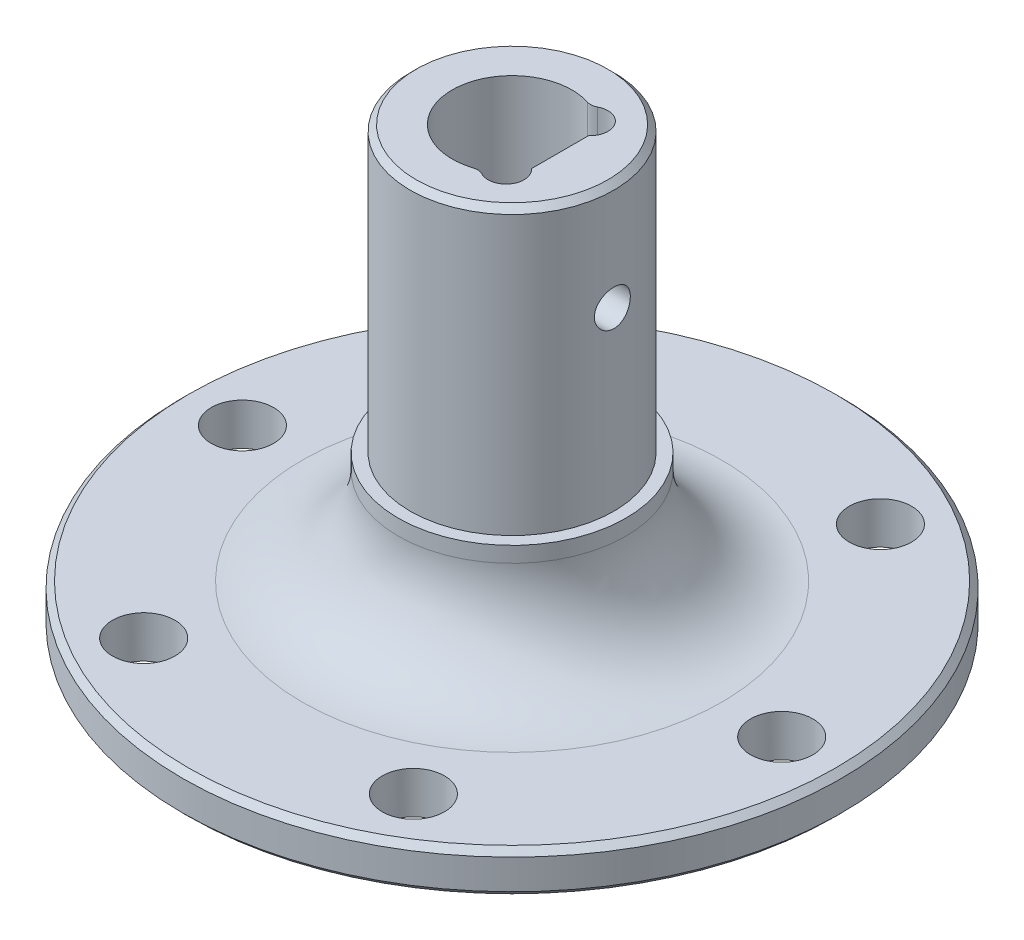
SolidWorks part; units mm, degrees
material "6061-T6 (SS)"
ref_plane "前视基准面" through (0, 0, 0) normal (0, 0, 1) x (1, 0, 0)
ref_plane "上视基准面" through (0, 0, 0) normal (0, 1, 0) x (1, 0, 0)
ref_plane "右视基准面" through (0, 0, 0) normal (1, 0, 0) x (0, 0, -1)
sketch "草图1" plane through (0, 0, 0) normal (0, 1, 0) x (1, 0, 0)
  circle A0 centre (0, 0) radius 10
  dimension "D1" = 20
extrude "凸台-拉伸1" add sketch "草图1" along normal blind 1
sketch "草图2" plane through (0, 1, 0) normal (0, 1, 0) x (1, 0, 0)
  circle A0 centre (0, 0) radius 27.5
  dimension "D1" = 55
extrude "凸台-拉伸2" add sketch "草图2" along normal blind 3.5
sketch "草图3" plane through (0, 4.5, 0) normal (0, 1, 0) x (1, 0, 0)
  circle A0 centre (0, 0) radius 8.5
  dimension "D1" = 17
extrude "凸台-拉伸3" add sketch "草图3" along normal blind 33
sketch "草图4" plane through (0, 37.5, 0) normal (0, 1, 0) x (1, 0, 0)
  circle A0 centre (0, 0) radius 5
  dimension "D1" = 10
extrude "切除-拉伸1" cut sketch "草图4" against normal blind 20
sketch "草图7" plane through (0, 1, 0) normal (0, -1, 0) x (1, 0, 0)
  line L0 (0, 0) -> (50.0994, 0) construction
  circle A0 centre (0, -22.5) radius 2.6
  circle A1 centre (-19.4856, 11.25) radius 2.6
  circle A2 centre (19.4856, 11.25) radius 2.6
  circle A3 centre (0, 23.75) radius 2.6
  circle A4 centre (20.5681, -11.875) radius 2.6
  circle A5 centre (-20.5681, -11.875) radius 2.6
  point P15 (0, 0)
  point P19 (0, 0)
  dimension "D1" = 22.5
  dimension "D2" = 5.2
  dimension "D4" = 47.5
  dimension "D3" = 3
  dimension "D5" = 3
extrude "切除-拉伸3" [suppressed] cut sketch "草图7" against normal blind 20
sketch "草图8" plane through (0, 0, 0) normal (0, -1, 0) x (1, 0, 0)
  line L0 (30.3203, 0) -> (-15.2916, 0) construction
  line L1 (4, 3) -> (4, -3)
  arc A0 (4, -3) -> (4, 3) centre (0, 0) ccw
  dimension "D1" = 10
  dimension "D2" = 4
extrude "凸台-拉伸4" add sketch "草图8" against normal up to surface (37.5 mm away) up to face at (0, 37.5, 5)
sketch "草图9" plane through (4, 0, 0) normal (-1, 0, 0) x (0, 0, 1)
  line L0 (0, -9.9189) -> (0, 47.6037) construction
  line L1 (8.5, 37.5) -> (-8.5, 37.5) construction
  circle A0 centre (0, 28.5) radius 1.5
  dimension "D1" = 3
  dimension "D2" = 9
extrude "切除-拉伸4" cut sketch "草图9" against normal mid plane 30
sketch "草图10" plane through (0, 4.5, 0) normal (0, 1, 0) x (1, 0, 0)
  circle A0 centre (0, 0) radius 8.5
  circle A1 centre (0, 0) radius 9.5
  dimension "D1" = 17
  dimension "D2" = 19
extrude "凸台-拉伸5" add sketch "草图10" along normal blind 9.3
fillet "圆角2" radius 8 1 edges at (0, 4.5, 9.5)
chamfer "倒角1" distance 0.5 angle 45 1 edges at (0, 4.5, 27.5)
chamfer "倒角2" distance 0.5 angle 45 1 edges at (0, 37.5, 8.5)
sketch "草图11" plane through (0, 37.5, 0) normal (0, 1, 0) x (1, 0, 0)
  circle A0 centre (0, 0) radius 8.5
  circle A1 centre (0, 0) radius 7.5
  circle A2 centre (0, 0) radius 8.5 construction
  dimension "D1" = 15
extrude "切除-拉伸5" [suppressed] cut sketch "草图11" against normal blind 1 from offset 19.5 offset against normal yes
sketch "草图12" plane through (0, 37.5, 0) normal (0, 1, 0) x (1, 0, 0)
  line L0 (0, 0) -> (6.142, 0) construction
  line L1 (4, -3) -> (4, 3) construction
  circle A0 centre (3, 3.5) radius 1.5
  circle A1 centre (3, -3.5) radius 1.5
  dimension "D1" = 3
  dimension "D2" = 7
  dimension "D3" = 1
extrude "切除-拉伸6" cut sketch "草图12" against normal up to surface (20 mm away) up to face at (-0.5, 17.5, 0)
sketch "草图13" plane through (0, 17.5, 0) normal (0, 1, 0) x (1, 0, 0)
  circle A0 centre (0, 0) radius 3.75
  dimension "D1" = 7.5
extrude "切除-拉伸7" cut sketch "草图13" against normal through all
fillet "圆角3" radius 1 2 edges at (1.9737, 27.5, 4.594) (1.9737, 27.5, -4.594)
chamfer "倒角3" distance 0.5 angle 45 1 edges at (0, 1, 27.5)
sketch "草图14" plane through (0, 1, 0) normal (0, -1, 0) x (1, 0, 0)
  circle A0 centre (0, 0) radius 22.5 construction
  circle A1 centre (22.5, 0) radius 2.6
  circle A2 centre (11.25, -19.4856) radius 2.6
  circle A3 centre (-11.25, -19.4856) radius 2.6
  circle A4 centre (-22.5, 0) radius 2.6
  circle A5 centre (-11.25, 19.4856) radius 2.6
  circle A6 centre (11.25, 19.4856) radius 2.6
  point P17 (0, 0)
  dimension "D1" = 5.2
  dimension "D3" = 45
  dimension "D2" = 6
extrude "切除-拉伸8" cut sketch "草图14" against normal blind 10
